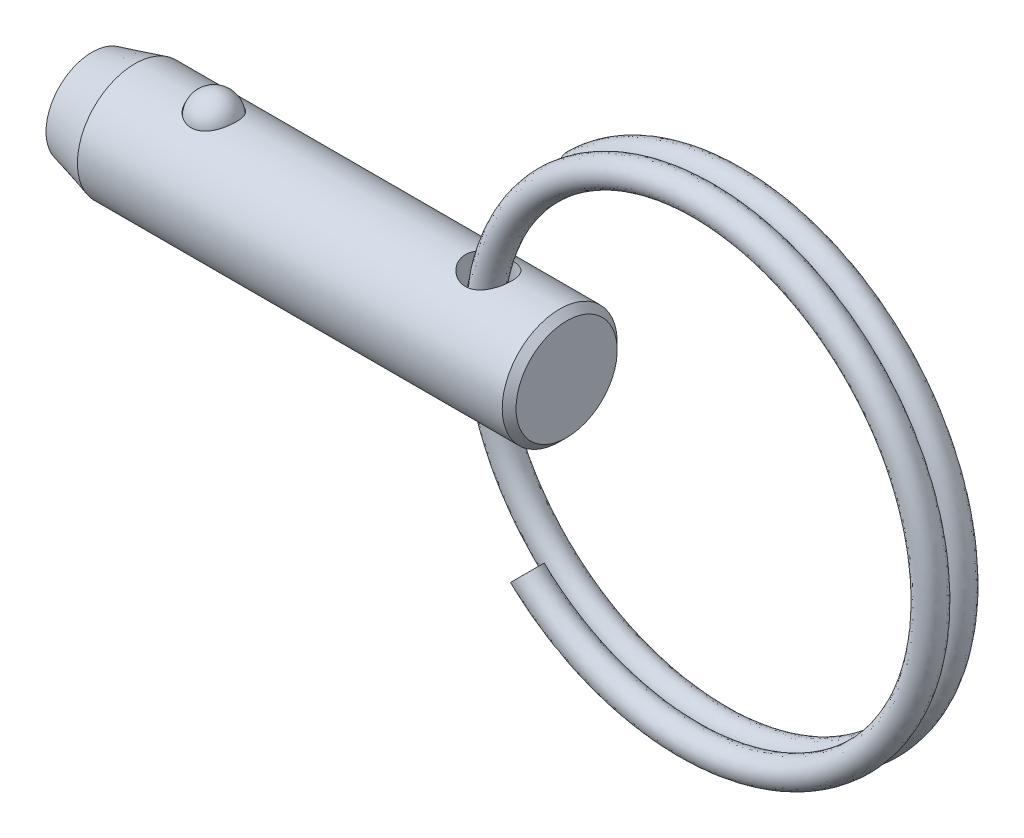
SolidWorks part; units mm, degrees
ref_plane "Front" through (0, 0, 0) normal (0, 0, 1) x (1, 0, 0)
ref_plane "Top" through (0, 0, 0) normal (0, 1, 0) x (1, 0, 0)
ref_plane "Right" through (0, 0, 0) normal (1, 0, 0) x (0, 0, -1)
sketch "Sketch1" plane through (0, 0, 0) normal (0, 0, 1) x (1, 0, 0)
  line L0 (5.588, 2.794) -> (5.207, 3.175)
  line L1 (5.207, 3.175) -> (5.588, 3.175) construction
  line L4 (5.588, 2.794) -> (5.588, 0)
  line L5 (5.588, 3.175) -> (5.588, 2.794) construction
  line L16 (5.207, 3.175) -> (-18.2549, 3.175)
  line L17 (-20.6248, 3.175) -> (-20.6248, 2.54) construction
  line L19 (-18.2549, 3.175) -> (-20.6248, 3.175) construction
  line L22 (-20.6248, -3.175) -> (-18.2549, -3.175) construction
  line L23 (-13.8903, 2.8575) -> (-13.8903, -2.8575) construction
  line L24 (-20.6248, 0) -> (5.588, 0)
  line L27 (5.588, 0) -> (8.382, 0) construction
  line L29 (-20.6248, 0) -> (-20.6248, -2.54) construction
  line L36 (0, 0) -> (0, 3.175) construction
  line L37 (-20.6248, 2.54) -> (-20.6248, 0)
  line L38 (-18.2549, -3.175) -> (5.588, -3.175) construction
  line L39 (-20.6248, -2.54) -> (-20.6248, -3.175) construction
  line L40 (-18.2549, 3.175) -> (-20.6248, 2.54)
  line L42 (-18.2549, -3.175) -> (-20.6248, -2.54) construction
  line L43 (-18.2549, 3.175) -> (-18.2549, -3.175) construction
  circle A2 centre (-13.8903, 2.8575) radius 1.2319 construction
  point P35 (-12.7, 3.175)
  dimension "D2" = 5.715
  dimension "D11" = 0.9144
  dimension "A" = 6.35
  dimension "D" = 5.588
  dimension "E" = 7.2644
  dimension "D3" = 0.381
  dimension "Useable Length" = 12.7
  dimension "D12" = 5.08
  dimension "C" = 7.9248
  dimension "A1" = 15
revolve "Revolve1" add sketch "Sketch1" angle 360 about L27
sketch "Sketch2" plane through (0, 0, 0) normal (0, 0, 1) x (1, 0, 0)
  line L0 (-12.633, 2.8575) -> (-15.1476, 2.8575)
  line L1 (-13.8903, 4.0894) -> (-13.8903, 4.1148) construction
  line L2 (-12.633, 2.8575) -> (-10.1184, 2.8575) construction
  circle A0 centre (-13.8903, 2.8575) radius 1.2319 construction
  circle A1 centre (-13.8903, 2.8575) radius 1.2319 construction
  arc A2 (-15.1476, 2.8575) -> (-12.633, 2.8575) centre (-13.8903, 2.8575) cw
  dimension "D1" = 0.0254
revolve "Cut-Revolve1" cut sketch "Sketch2" angle 360 about L2
sketch "Sketch3" plane through (0, 0, 0) normal (0, 0, 1) x (1, 0, 0)
  line L0 (-12.6584, 2.8575) -> (-15.1222, 2.8575)
  line L1 (-12.6584, 2.8575) -> (-10.1946, 2.8575) construction
  circle A0 centre (-13.8903, 2.8575) radius 1.2319 construction
  arc A1 (-12.6584, 2.8575) -> (-15.1222, 2.8575) centre (-13.8903, 2.8575) ccw
revolve "Revolve2" add sketch "Sketch3" angle 360 about L1
sketch "Sketch4" plane through (0, 0, 0) normal (0, 0, 1) x (1, 0, 0)
  line L1 (1.27, -3.175) -> (2.54, -3.175)
  line L2 (1.27, -3.175) -> (1.27, 3.175)
  line L3 (1.27, 3.175) -> (2.54, 3.175)
  line L4 (2.54, -3.175) -> (2.54, 3.175)
  line L5 (1.27, -3.175) -> (1.27, -4.445) construction
  line L6 (2.54, 3.175) -> (5.588, 3.175) construction
  line L8 (0, -3.175) -> (0, 3.175) construction
  line L9 (0, 0) -> (1.27, 0) construction
  line L11 (1.27, 0) -> (2.54, 0) construction
  line L12 (5.207, 3.175) -> (-18.2549, 3.175) construction
  line L14 (-18.2549, -3.175) -> (5.588, -3.175) construction
  dimension "D1" = 2.54
revolve "Cut-Revolve2" cut sketch "Sketch4" angle 360 about L2
sketch "Sketch5" plane through (0, 0, 0) normal (0, 0, 1) x (1, 0, 0)
  line L0 (0, 0) -> (0.293, 0) construction
  line L1 (0.293, 0) -> (0.293, 3.175) construction
  line L2 (5.207, 3.175) -> (-18.2549, 3.175) construction
  line L3 (13.755, 0) -> (27.217, 0) construction
  line L4 (2.54, 3.175) -> (2.247, 3.175) construction
  line L5 (1.27, 3.175) -> (2.54, 3.175) construction
  line L6 (0.6728, 3.175) -> (0.6728, -3.175) construction
  line L7 (0.293, 3.175) -> (0, 3.175) construction
  line L8 (1.27, -3.175) -> (2.54, -3.175) construction
  line L9 (0.6728, -3.175) -> (2.54, -3.175) construction
  line L10 (0.293, 0) -> (13.755, 0) construction
  line L11 (13.755, 0) -> (8.7098, -10.8195) construction
  line L12 (2.247, 3.175) -> (0.6728, 3.175) construction
  line L13 (13.755, 11.938) -> (13.755, 13.462) construction
  line L14 (8.7098, -10.8195) -> (8.3878, -11.5101) construction
  circle A0 centre (13.755, 0) radius 13.462
  circle A1 centre (13.755, 0) radius 11.938 construction
  circle A2 centre (13.755, 0) radius 12.7 construction
  point P26 (13.755, 12.7)
  dimension "D1" = 65
  dimension "R Ring Dia" = 25.4
  dimension "Ring OD" = 1.524
curve "Helix/Spiral1" pitch 1.5494 height 1.3557 radius 13.462 left hand yes centre (13.755, 0, 0) axis (0, 0, -1) start towards (1, 0, 0)
sketch "Sketch6" plane through (114.0038, 0, 0) normal (0, 1, 0) x (0, 0, -1)
  line L0 (0, 112.1868) -> (0, 112.9488) construction
  line L1 (0, 112.9488) -> (0, 113.7108) construction
  circle A0 centre (0, 112.9488) radius 0.762
  dimension "D1" = 1.524
sketch "Sketch7" plane through (0, 0, 0) normal (0, 0, 1) x (1, 0, 0)
  circle A0 centre (13.755, 0) radius 13.462 construction
  circle A1 centre (13.755, 0) radius 13.462
curve "Helix/Spiral2" pitch 1.5494 height 1.3557 radius 13.462 left hand yes centre (13.755, 0, 0) axis (0, 0, 1) start towards (1, 0, 0)
sweep "Sweep1" add profiles "Sketch6" path "Helix/Spiral1"
sweep "Sweep2" add profiles "Sketch6<2>" path "Helix/Spiral2"
sketch "Sketch6<2>" plane through (114.0038, 0, 0) normal (0, 1, 0) x (0, 0, -1) same geometry as "Sketch6"
ref_plane "Plane1" through (0, -10.8195, 0) normal (0, 1, 0) x (-1, 0, 0)
sketch "Sketch8" plane through (0, -10.8195, 0) normal (0, 1, 0) x (-1, 0, 0)
  line L0 (143.6902, 0) -> (-8.7098, 0) construction
  line L1 (10.3402, -0.7779) -> (4.5066, -0.7779)
  line L2 (3.5004, -0.9415) -> (-7.2005, -4.517)
  line L3 (-7.2005, 4.517) -> (3.5004, 0.9415)
  line L4 (4.5066, 0.7779) -> (130.4738, 0.7779)
  line L5 (131.48, 0.9415) -> (142.1809, 4.517)
  line L6 (124.6402, -0.7779) -> (130.4738, -0.7779)
  line L7 (131.48, -0.9415) -> (142.1809, -4.517)
  line L8 (10.3402, -0.7779) -> (10.3402, 0.7779) construction
  arc A0 (-7.2005, 4.517) -> (-7.2005, -4.517) centre (-8.7098, 0) ccw
  arc A1 (142.1809, -4.517) -> (142.1809, 4.517) centre (143.6902, 0) ccw
  arc A2 (4.5066, -0.7779) -> (3.5004, -0.9415) centre (4.5066, -3.9529) ccw
  arc A3 (3.5004, 0.9415) -> (4.5066, 0.7779) centre (4.5066, 3.9529) ccw
  arc A4 (130.4738, -0.7779) -> (131.48, -0.9415) centre (130.4738, -3.9529) cw
  arc A5 (130.4738, 0.7779) -> (131.48, 0.9415) centre (130.4738, 3.9529) ccw
  point P6 (10.3402, 0)
  point P16 (3.9902, -0.7779)
  point P20 (3.9902, 0.7779)
  point P23 (130.9902, -0.7779)
  point P26 (130.9902, 0.7779)
  dimension "D2" = 4.7625
  dimension "D3" = 1.5557
  dimension "D6" = 3.175
  dimension "Lanyard Length" = 152.4
  dimension "D4" = 6.35
  dimension "D5" = 12.7
ref_plane "Plane2" through (-10.3402, 0, 0) normal (1, 0, 0) x (0, 0, -1)
sketch "Sketch9" plane through (-10.3402, 0, 0) normal (1, 0, 0) x (0, 0, -1)
  circle A0 centre (0.7779, -10.8195) radius 0.7779
sweep "Sweep3" [suppressed] add profiles "Sketch9" path "Sketch8"
sketch "Sketch10" [suppressed] plane through (-10.3402, 0, 0) normal (1, 0, 0) x (0, 0, -1)
  arc A0 (-0.3849, -10.1482) -> (-0.3849, -11.4908) centre (-0.7779, -10.8195) ccw
  circle A1 centre (0.7779, -10.8195) radius 0.7779
  arc A2 (0.3849, -11.4908) -> (0.3849, -10.1482) centre (0.7779, -10.8195) ccw
  arc A3 (-0.3849, -11.4908) -> (0.3849, -11.4908) centre (0, -12.1485) cw
  arc A4 (-0.3869, -9.3301) -> (-0.3869, -12.3089) centre (-0.7779, -10.8195) ccw
  arc A5 (0.3869, -12.3089) -> (0.3869, -9.3301) centre (0.7779, -10.8195) ccw
  circle A6 centre (-0.7779, -10.8195) radius 1.5399 construction
  circle A7 centre (-0.7779, -10.8195) radius 0.7779 construction
  arc A8 (-0.3849, -10.1482) -> (0.3849, -10.1482) centre (0, -9.4905) ccw
  arc A9 (-0.3869, -9.3301) -> (0.3869, -9.3301) centre (0, -7.856) ccw
  arc A10 (0.3869, -12.3089) -> (-0.3869, -12.3089) centre (0, -13.783) ccw
  point P4 (-0.034, -10.2746)
  point P8 (2.3178, -10.502)
  point P9 (0.762, -10.502)
  dimension "D3" = 1.524
  dimension "D4" = 0.762
  dimension "D2" = 0.762
  dimension "D1" = 0
extrude "Extrude1" [suppressed] add sketch "Sketch10" along normal blind 5.715 separate body
sketch "Sketch11" [suppressed] plane through (-124.6402, 0, 0) normal (1, 0, 0) x (0, 0, -1)
  arc A4 (-0.3849, -10.1482) -> (-0.3849, -11.4908) centre (-0.7779, -10.8195) ccw
  arc A5 (0.3849, -11.4908) -> (-0.3849, -11.4908) centre (0, -12.1485) ccw
  arc A6 (0.3849, -11.4908) -> (0.3849, -10.1482) centre (0.7779, -10.8195) ccw
  arc A7 (-0.3849, -10.1482) -> (0.3849, -10.1482) centre (0, -9.4905) ccw
  arc A8 (-0.3849, -10.1482) -> (-0.3849, -11.4908) centre (-0.7779, -10.8195) ccw
  arc A9 (0.3849, -11.4908) -> (-0.3849, -11.4908) centre (0, -12.1485) ccw
  arc A10 (0.3849, -11.4908) -> (0.3849, -10.1482) centre (0.7779, -10.8195) ccw
  arc A11 (-0.3849, -10.1482) -> (0.3849, -10.1482) centre (0, -9.4905) ccw
  arc A12 (-0.3869, -9.3301) -> (-0.3869, -12.3089) centre (-0.7779, -10.8195) ccw
  arc A13 (0.3869, -12.3089) -> (-0.3869, -12.3089) centre (0, -13.783) ccw
  arc A14 (0.3869, -12.3089) -> (0.3869, -9.3301) centre (0.7779, -10.8195) ccw
  arc A15 (-0.3869, -9.3301) -> (0.3869, -9.3301) centre (0, -7.856) ccw
  arc A16 (-0.3869, -9.3301) -> (-0.3869, -12.3089) centre (-0.7779, -10.8195) ccw
  arc A17 (0.3869, -12.3089) -> (-0.3869, -12.3089) centre (0, -13.783) ccw
  arc A18 (0.3869, -12.3089) -> (0.3869, -9.3301) centre (0.7779, -10.8195) ccw
  arc A19 (-0.3869, -9.3301) -> (0.3869, -9.3301) centre (0, -7.856) ccw
  dimension "D1" = 0
  dimension "D2" = 0
extrude "Extrude2" [suppressed] add sketch "Sketch11" against normal blind 5.715 separate body
sketch "Sketch12" plane through (0, -10.8195, 0) normal (0, 1, 0) x (-1, 0, 0)
  line L0 (174.4712, -5.2864) -> (168.9086, -5.2864) construction
  line L1 (174.4712, -5.9214) -> (158.1026, -5.9214)
  line L2 (174.4712, -5.9214) -> (174.4712, -4.6514)
  line L3 (174.4712, -4.6514) -> (158.3265, -4.6514)
  line L4 (158.1026, -5.9214) -> (158.3265, -4.6514) construction
  line L5 (158.1026, -5.9214) -> (142.7212, -0.3231)
  line L6 (168.9086, -5.2864) -> (158.2146, -5.2864) construction
  line L7 (158.3265, -4.6514) -> (143.1555, 0.8704)
  line L8 (142.7212, -0.3231) -> (143.1555, 0.8704)
  line L9 (158.2146, -5.2864) -> (148.1655, -1.6289) construction
  line L10 (148.1655, -1.6289) -> (142.9383, 0.2737) construction
  arc A0 (142.1809, -4.517) -> (142.1809, 4.517) centre (143.6902, 0) ccw construction
  dimension "D1" = 20
  dimension "D2" = 31.75
  dimension "D3" = 1.27
  dimension "D4" = 5.5626
extrude "Extrude3" [suppressed] add sketch "Sketch12" along normal mid plane 12.7 separate body
sketch "Sketch13" [suppressed] plane through (0, 0, -4.6514) normal (0, 0, 1) x (1, 0, 0)
  line L0 (-174.4712, -10.8195) -> (-158.3265, -10.8195) construction
  line L1 (-172.4782, -4.4695) -> (-174.4712, -4.4695)
  line L2 (-174.4712, -4.4695) -> (-158.3265, -4.4695) construction
  line L3 (-174.4712, -4.4695) -> (-176.4642, -4.4695)
  line L4 (-176.4642, -4.4695) -> (-176.4642, -17.1695)
  line L5 (-176.4642, -17.1695) -> (-174.4712, -17.1695)
  line L6 (-174.4712, -17.1695) -> (-172.4782, -17.1695)
  line L7 (-174.4712, -17.1695) -> (-158.3265, -17.1695) construction
  arc A0 (-172.4782, -4.4695) -> (-172.4782, -17.1695) centre (-163.3587, -10.8195) ccw
  circle A1 centre (-168.9086, -10.8195) radius 2.5781
  dimension "D1" = 5.1562
  dimension "D2" = 11.1125
extrude "Extrude4" [suppressed] cut sketch "Sketch13" against normal up to surface (1.27 mm away)
sketch "Sketch14" [suppressed] plane through (-17.0257, 0, 46.7778) normal (-0.342, 0, 0.9397) x (0.9397, 0, 0.342)
  line L3 (-136.2175, -4.4695) -> (-134.2245, -4.4695)
  line L4 (-134.2245, -4.4695) -> (-132.2315, -4.4695)
  line L5 (-132.2315, -4.4695) -> (-132.2315, -17.1695)
  line L6 (-132.2315, -17.1695) -> (-134.2245, -17.1695)
  line L7 (-134.2245, -17.1695) -> (-136.2175, -17.1695)
  line L8 (-134.2245, -4.4695) -> (-134.2245, -17.1695) construction
  line L9 (-150.3692, -4.4695) -> (-134.2245, -4.4695) construction
  line L10 (-150.4811, -10.8195) -> (-139.7871, -10.8195) construction
  arc A0 (-136.2175, -17.1695) -> (-136.2175, -4.4695) centre (-145.337, -10.8195) ccw
  circle A1 centre (-139.7871, -10.8195) radius 2.5781
  dimension "D1" = 5.1562
  dimension "D2" = 11.1125
extrude "Extrude6" [suppressed] cut sketch "Sketch14" against normal up to surface (1.27 mm away)
sketch "Sketch15" [suppressed] plane through (0, 0, 0) normal (0, 0, 1) x (1, 0, 0)
  line L1 (-258.031, -4.4695) -> (-99.281, -4.4695)
  line L2 (-258.031, -4.4695) -> (-270.731, -17.1695)
  line L3 (-270.731, -17.1695) -> (-111.981, -17.1695)
  line L4 (-99.281, -4.4695) -> (-111.981, -17.1695)
  line L5 (-325.1006, -4.4695) -> (-310.949, -4.4695) construction
  line L6 (-325.1006, -17.1695) -> (-310.949, -17.1695) construction
  circle A0 centre (-321.531, -10.8195) radius 2.5781 construction
  dimension "D1" = 63.5
  dimension "D2" = 158.75
  dimension "D3" = 45
extrude "Extrude7" [suppressed] cut sketch "Sketch15" against normal through all and the other way through all
move or copy body "Body-Move/Copy1" [suppressed] bodies to move or copy 147 151 144 copy no translate (152.4, 0, 0)
sketch "Sketch16" [suppressed] plane through (0, 0, 0) normal (0, 0, 1) x (1, 0, 0)
  line L0 (-111.981, -6.057) -> (-111.981, -9.232) construction
  line L1 (-111.981, -9.232) -> (-109.441, -8.2795) construction
  line L2 (-109.441, -8.2795) -> (-114.521, -13.3595) construction
  line L3 (-114.521, -13.3595) -> (-111.981, -12.407) construction
  line L4 (-111.981, -12.407) -> (-111.981, -15.582) construction
  line L5 (-112.7589, -11.5974) -> (-111.2032, -10.0416) construction
  line L6 (-105.631, -15.582) -> (-105.631, -12.407) construction
  line L7 (-105.631, -12.407) -> (-108.171, -13.3595) construction
  line L8 (-108.171, -13.3595) -> (-103.091, -8.2795) construction
  line L9 (-103.091, -8.2795) -> (-105.631, -9.232) construction
  line L10 (-105.631, -9.232) -> (-105.631, -6.057) construction
  line L11 (-104.8532, -10.0416) -> (-106.4089, -11.5974) construction
  line L14 (-4.7291, -10.8195) -> (-283.0963, -10.8195) construction
  dimension "D1" = 3.175
  dimension "D2" = 3.175
  dimension "D3" = 5.08
  dimension "D4" = 1.5875
equation "\"D12@Sketch1\"=\"A@Sketch1\" * 0.80"
equation "\"D2@Sketch1\"=\"A@Sketch1\" * 0.9"
equation "\"D1@Sketch4\" = \"A@Sketch1\" / 2.5"
equation "\"Ring OD@Sketch5\" = \"R Ring Dia@Sketch5\" * 0.06"
equation "\"D4@Helix/Spiral1\"=\"Ring OD@Sketch5\" + 0.001"
equation "\"D1@Sketch6\"=\"Ring OD@Sketch5\""
equation "\"D4@Helix/Spiral2\" = \"D4@Helix/Spiral1\""
equation "\"D5@Helix/Spiral2\" = \"D5@Helix/Spiral1\""
equation "\"D1@Sketch14\" = \"D1@Sketch13\""
equation "\"D2@Sketch14\" = \"D2@Sketch13\""
